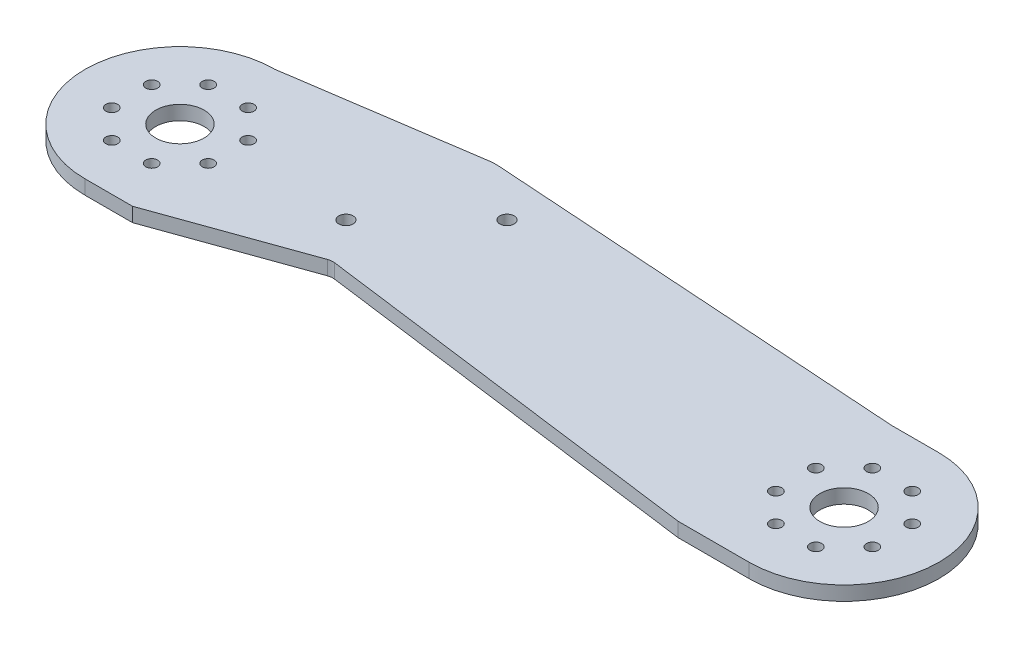
SolidWorks part; units mm, degrees
ref_plane "Front" through (0, 0, 0) normal (0, 0, 1) x (1, 0, 0)
ref_plane "Top" through (0, 0, 0) normal (0, 1, 0) x (1, 0, 0)
ref_plane "Right" through (0, 0, 0) normal (1, 0, 0) x (0, 0, -1)
sketch "Sketch1" plane through (0, 0, 0) normal (0, 1, 0) x (1, 0, 0)
  line L0 (-70, 0) -> (70, 0) construction
  line L1 (70, 0) -> (59.8373, 4.2095) construction
  line L2 (70, 20) -> (-70, 20)
  line L4 (-70, -20) -> (-41, -20)
  line L5 (0, 20) -> (0, -20) construction
  line L7 (-70, 0) -> (-59.8373, 4.2095) construction
  line L8 (-16.5, -20) -> (-28.75, -7.75)
  line L9 (-28.75, -7.75) -> (-41, -20)
  line L10 (-35, 0) -> (-18.0294, 16.9706) construction
  line L11 (-16.5, -20) -> (70, -20)
  circle A0 centre (70, 0) radius 5.1
  circle A1 centre (59.8373, 4.2095) radius 1.25
  arc A2 (70, -20) -> (70, 20) centre (70, 0) ccw
  circle A3 centre (65.7905, 10.1627) radius 1.25
  circle A4 centre (74.2095, 10.1627) radius 1.25
  circle A5 centre (80.1627, 4.2095) radius 1.25
  circle A6 centre (80.1627, -4.2095) radius 1.25
  circle A7 centre (74.2095, -10.1627) radius 1.25
  circle A13 centre (65.7905, -10.1627) radius 1.25
  circle A14 centre (59.8373, -4.2095) radius 1.25
  circle A15 centre (-59.8373, -4.2095) radius 1.25
  circle A16 centre (-65.7905, -10.1627) radius 1.25
  circle A17 centre (-74.2095, -10.1627) radius 1.25
  circle A18 centre (-80.1627, -4.2095) radius 1.25
  circle A19 centre (-80.1627, 4.2095) radius 1.25
  circle A20 centre (-74.2095, 10.1627) radius 1.25
  circle A21 centre (-65.7905, 10.1627) radius 1.25
  arc A22 (-70, -20) -> (-70, 20) centre (-70, 0) cw
  circle A23 centre (-59.8373, 4.2095) radius 1.25
  circle A24 centre (-70, 0) radius 5.1
  circle A25 centre (-35, 0) radius 1.5
  circle A26 centre (-18.0294, 16.9706) radius 1.5
  point P19 (70, 0)
  point P24 (0, 0)
  dimension "D1" = 2.5
  dimension "D2" = 10.2
  dimension "D4" = 40
  dimension "D9" = 16.5
  dimension "D10" = 24
  dimension "D11" = 35
  dimension "D12" = 3
  dimension "D3" = 11
  dimension "D5" = 22.5
  dimension "D7" = 70
  dimension "D8" = 41
  dimension "D13" = 45
  dimension "D6" = 8
extrude "Boss-Extrude1" add sketch "Sketch1" along normal blind 3
fillet "Fillet1" radius 3 3 edges at (-16.5, 1.5, 20) (-41, 1.5, 20) (-28.75, 1.5, 7.75)
sketch "Sketch2" plane through (0, 0, 0) normal (0, -1, 0) x (1, 0, 0)
  line L0 (-28.3582, 9.0183) -> (55, 20)
  line L1 (-15.2574, 20) -> (70, 20) construction
  line L2 (-28.3582, 9.0183) -> (-28.3582, 26.5584)
  line L3 (-28.3582, 26.5584) -> (55, 20)
  arc A0 (-30.8713, 9.8713) -> (-26.6287, 9.8713) centre (-28.75, 11.9926) ccw construction
  circle A1 centre (70, 0) radius 5.1 construction
  dimension "D1" = 15
extrude "Cut-Extrude1" cut sketch "Sketch2" against normal blind 10
sketch "Sketch3" plane through (0, 0, 0) normal (0, -1, 0) x (1, 0, 0)
  line L0 (-70, -20) -> (-29.7142, -26)
  line L1 (-29.7142, -26) -> (60, -20)
  line L2 (70, -20) -> (-70, -20) construction
  line L3 (-70, -20) -> (60, -20)
  line L4 (-29.7142, 9.1518) -> (-29.7142, -26) construction
  arc A0 (-70, 20) -> (-70, -20) centre (-70, 0) ccw construction
  circle A1 centre (70, 0) radius 5.1 construction
  arc A2 (-30.8713, 9.8713) -> (-28.3582, 9.0183) centre (-28.75, 11.9926) ccw construction
  dimension "D1" = 10
  dimension "D2" = 6
extrude "Boss-Extrude2" add sketch "Sketch3" against normal up to surface (3 mm away) up to face at (-9.6228, 3, 8.6588)
sketch "Sketch4" plane through (0, 0, 0) normal (0, -1, 0) x (1, 0, 0)
  line L0 (-29.7617, 9.1684) -> (-60, 20)
  line L1 (-70, 20) -> (-42.2426, 20) construction
  line L2 (-60, 20) -> (-60.5296, 25.5787)
  line L3 (-60.5296, 25.5787) -> (-29.9984, 24.4018)
  line L4 (-29.9984, 24.4018) -> (-29.7617, 9.1684)
  arc A0 (-30.8713, 9.8713) -> (-28.3582, 9.0183) centre (-28.75, 11.9926) ccw construction
  circle A1 centre (-70, 0) radius 5.1 construction
  dimension "D1" = 10
extrude "Cut-Extrude2" cut sketch "Sketch4" against normal blind 10
fillet "Fillet2" radius 10 2 edges at (60, 1.5, -20) (-29.7142, 1.5, -26)
equation "\"2ю5\"=6.64855"
